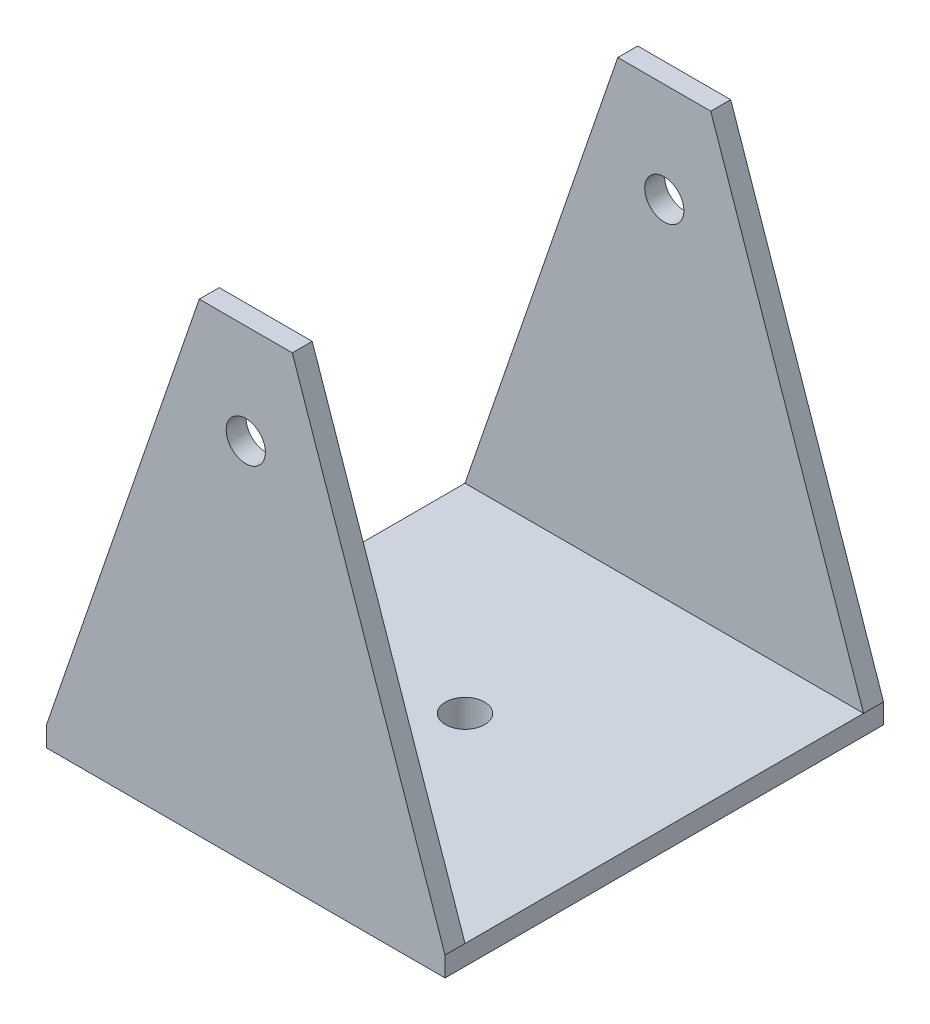
SolidWorks part; units mm, degrees
ref_plane "Front Plane" through (0, 0, 0) normal (0, 0, 1) x (1, 0, 0)
ref_plane "Top Plane" through (0, 0, 0) normal (0, 1, 0) x (1, 0, 0)
ref_plane "Right Plane" through (0, 0, 0) normal (1, 0, 0) x (0, 0, -1)
sketch "Sketch1" plane through (0, 0, 0) normal (0, 1, 0) x (1, 0, 0)
  line L1 (-30, 30) -> (30, 30)
  line L2 (-30, 30) -> (-30, -30)
  line L3 (-30, -30) -> (30, -30)
  line L4 (30, 30) -> (30, -30)
  line L5 (-30, 30) -> (30, -30) construction
  line L6 (-30, -30) -> (30, 30) construction
  circle A0 centre (0, 0) radius 2.95
  point P0 (0, 0)
  dimension "D1" = 60
extrude "Boss-Extrude1" add sketch "Sketch1" along normal blind 3
sketch "Sketch2" plane through (0, 0, 0) normal (0, -1, 0) x (1, 0, 0)
  circle A0 centre (0, 0) radius 4.5
  circle A1 centre (0, 0) radius 2.95
extrude "Boss-Extrude2" add sketch "Sketch2" along normal blind 2
sketch "Sketch3" plane through (0, 3, 0) normal (0, 1, 0) x (1, 0, 0)
  line L0 (0, 0) -> (0, 30) construction
  line L1 (30, 30) -> (-30, 30) construction
  line L2 (0, 30) -> (-30, 30) construction
  line L3 (-30, 30) -> (-30, 0) construction
  line L4 (-30, 30) -> (-30, -30) construction
  line L5 (-30, 0) -> (0, 0) construction
sketch "Sketch4" plane through (0, 0, -30) normal (0, 0, -1) x (-1, 0, 0)
  line L0 (-30, 0) -> (30, 0)
  line L1 (-30, 0) -> (-30, 70)
  line L2 (30, 0) -> (30, 70) construction
  line L3 (-30, 70) -> (30, 70)
  line L4 (-30, 0) -> (30, 70) construction
  line L5 (30, 0) -> (-30, 70) construction
  line L6 (-7, 70) -> (7, 70)
  line L7 (7, 70) -> (30, 3)
  line L8 (30, 3) -> (30, 1.1464)
  line L9 (30, 3) -> (30, 0)
  line L10 (-30, 0) -> (-30, 3)
  line L11 (-30, 3) -> (-7, 70)
  point P7 (0, 35)
  point P10 (0, 70)
  line M5 (-30, 0) -> (30, 0)
  line M6 (30, 0) -> (30, 3)
  line M7 (30, 3) -> (-30, 3)
  line M8 (-30, 3) -> (-30, 0)
extrude "Boss-Extrude3" add sketch "Sketch4" along normal blind 3 contours L11 L7 L3 M7 | M8 M5 M6 M7 region at (0, 1.5, -30) region at (0, 29.5586, -30)
ref_plane "Plane1" through (0, 0, 0) normal (0, 0, 1) x (1, 0, 0)
sketch "Sketch5" plane through (0, 0, -33) normal (0, 0, -1) x (-1, 0, 0)
  line L0 (0, 70) -> (0, 55) construction
  line L1 (-7, 70) -> (7, 70) construction
  circle A0 centre (0, 55) radius 2.95
extrude "Cut-Extrude1" cut sketch "Sketch5" against normal blind 3
mirror "Mirror2" about plane through (0, 0, 0) normal (0, 0, 1) of "Boss-Extrude1", "Boss-Extrude3", "Cut-Extrude1"
sketch "Sketch6" plane through (0, 0, 33) normal (0, 0, 1) x (1, 0, 0)
  line L0 (0, 70) -> (0, 51) construction
  line L1 (7, 70) -> (-7, 70) construction
